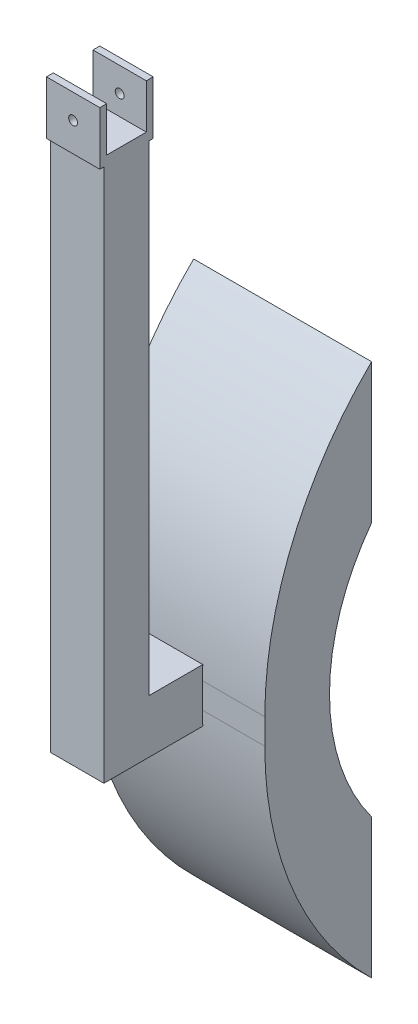
SolidWorks part; units mm, degrees
ref_plane "前视基准面" through (0, 0, 0) normal (0, 0, 1) x (1, 0, 0)
ref_plane "上视基准面" through (0, 0, 0) normal (0, 1, 0) x (1, 0, 0)
ref_plane "右视基准面" through (0, 0, 0) normal (1, 0, 0) x (0, 0, -1)
other "Configuration Table"
sketch "草图1" plane through (0, 0, 0) normal (0, 1, 0) x (1, 0, 0)
  line L1 (-15, 11.1535) -> (15, 11.1535)
  line L2 (-15, 11.1535) -> (-15, -11.1535)
  line L3 (-15, -11.1535) -> (15, -11.1535)
  line L4 (15, 11.1535) -> (15, -11.1535)
  line L5 (-15, 11.1535) -> (15, -11.1535) construction
  line L6 (-15, -11.1535) -> (15, 11.1535) construction
  point P0 (0, 0)
  dimension "D1" = 30
  dimension "D2" = 22.307
extrude "凸台-拉伸1" add sketch "草图1" along normal mid plane 5
sketch "草图4" plane through (0, 2.5, 0) normal (0, 1, 0) x (1, 0, 0)
  line L0 (15, -11.1535) -> (15, 11.1535) construction
  line L1 (-15, 15) -> (15, 15)
  line L2 (-15, 15) -> (-15, -15)
  line L3 (-15, -15) -> (15, -15)
  line L4 (15, 15) -> (15, -15)
  line L5 (-15, 15) -> (15, -15) construction
  line L6 (-15, -15) -> (15, 15) construction
  point P0 (0, 0)
  line M3 (15, 11.1535) -> (-15, 11.1535)
  line M5 (-15, -11.1535) -> (15, -11.1535)
  dimension "D1" = 30
extrude "凸台-拉伸5" add sketch "草图4" along normal blind 30 from surface contours L4 L2 L3 M5 | L4 L1 L2 M3 region at (0, 2.5, -13.0767) region at (0, 2.5, 13.0768) starting at face at (0, -2.5, 0)
sketch "草图5" plane through (0, 0, 15) normal (0, 0, 1) x (1, 0, 0)
  line L0 (-15, -2.5) -> (15, -2.5) construction
  circle A0 centre (0, 13.784) radius 2.5
  dimension "D1" = 5
  dimension "D2" = 16.284
extrude "切除-拉伸1" cut sketch "草图5" against normal through all
sketch "草图6" plane through (0, -2.5, 0) normal (0, -1, 0) x (1, 0, 0)
  line L1 (-15, 12.72) -> (15, 12.72)
  line L2 (-15, 12.72) -> (-15, -12.72)
  line L3 (-15, -12.72) -> (15, -12.72)
  line L4 (15, 12.72) -> (15, -12.72)
  line L5 (-15, 12.72) -> (15, -12.72) construction
  line L6 (-15, -12.72) -> (15, 12.72) construction
  point P0 (0, 0)
  dimension "D1" = 25.44
  dimension "D2" = 30
extrude "凸台-拉伸6" add sketch "草图6" along normal blind 300
sketch "草图8" plane through (0, 0, -12.72) normal (0, 0, -1) x (-1, 0, 0)
  line L0 (15, -302.5) -> (15, -2.5) construction
  line L1 (-15, -302.5) -> (15, -302.5)
  line L2 (-15, -302.5) -> (-15, -272.5)
  line L3 (-15, -272.5) -> (15, -272.5)
  line L4 (15, -302.5) -> (15, -272.5)
  dimension "D1" = 30
extrude "凸台-拉伸8" add sketch "草图8" along normal blind 30
sketch "草图10" plane through (0, 0, -42.72) normal (0, 0, -1) x (-1, 0, 0)
  line L0 (-15, -287.5) -> (0, -287.5) construction
  line L2 (-50, -137.5) -> (50, -137.5)
  line L3 (-50, -137.5) -> (-50, -437.5)
  line L4 (-15, -272.5) -> (-15, -302.5)
  line L5 (-15, -302.5) -> (15, -302.5)
  line L6 (15, -302.5) -> (15, -272.5)
  line L7 (15, -272.5) -> (-15, -272.5)
  line L8 (-15, -272.5) -> (-15, -302.5) construction
  line L9 (-15, -302.5) -> (15, -302.5) construction
  line L10 (15, -302.5) -> (15, -272.5) construction
  line L11 (15, -272.5) -> (-15, -272.5) construction
  line L12 (-50, -437.5) -> (50, -437.5)
  line L13 (50, -137.5) -> (50, -437.5)
  line L14 (-50, -137.5) -> (50, -437.5) construction
  line L15 (-50, -437.5) -> (50, -137.5) construction
  dimension "D2" = 300
  dimension "D3" = 100
  dimension "D1" = 0
extrude "凸台-拉伸9" add sketch "草图10" along normal blind 60
fillet "圆角1" radius 200 1 edges at (0, -437.5, -42.72)
fillet "圆角2" radius 200 1 edges at (0, -137.5, -42.72)
sketch "草图11" plane through (50, 0, 0) normal (1, 0, 0) x (0, 0, -1)
  line L0 (102.72, -137.5) -> (102.72, -437.5) construction
  line L1 (42.72, -287.5) -> (138.9184, -287.5) construction
  line L2 (42.72, -280.3286) -> (42.72, -294.6714) construction
  arc A0 (102.72, -215.9988) -> (102.72, -359.0012) centre (199.0921, -287.5) ccw
  dimension "D1" = 120
extrude "切除-拉伸3" cut sketch "草图11" against normal through all and the other way through all contours A0
